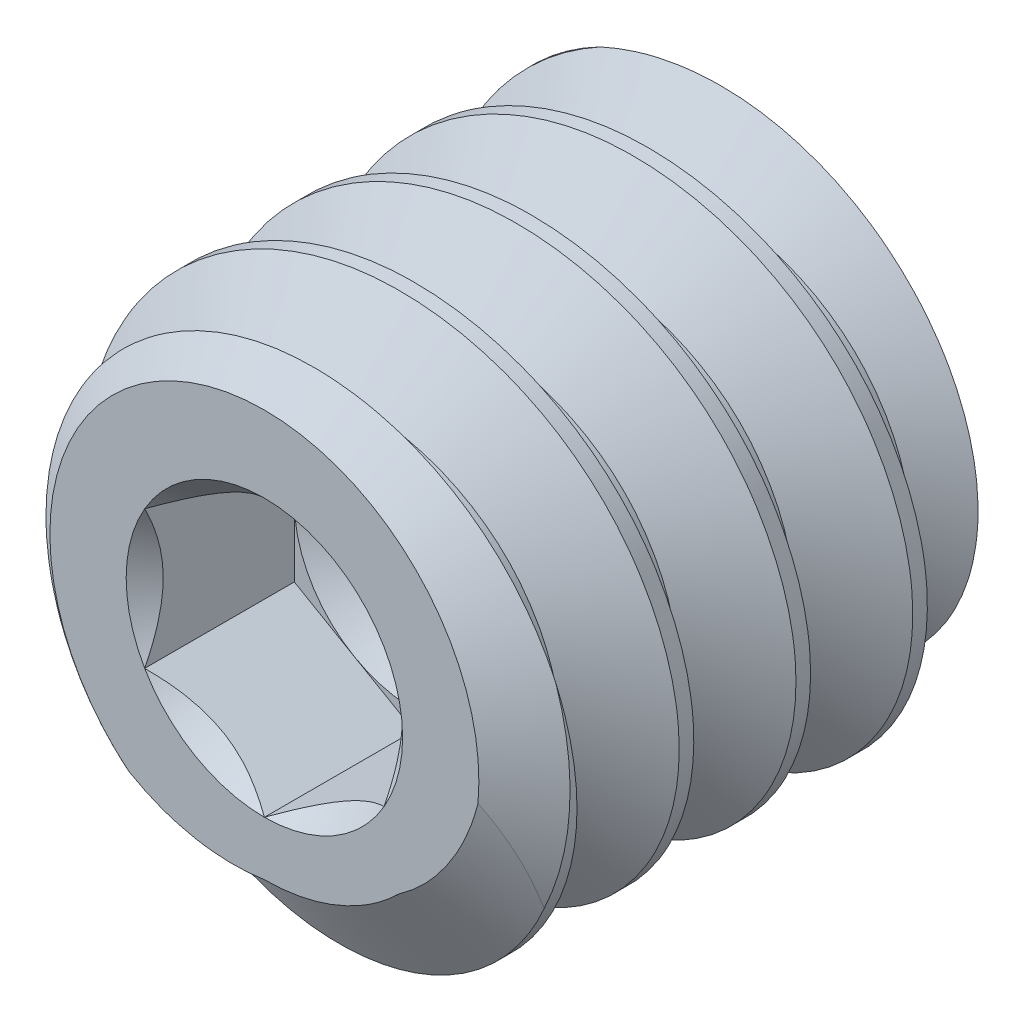
SolidWorks part; units mm, degrees
ref_plane "Front" through (0, 0, 0) normal (0, 0, 1) x (1, 0, 0)
ref_plane "Top" through (0, 0, 0) normal (0, 1, 0) x (1, 0, 0)
ref_plane "Right" through (0, 0, 0) normal (1, 0, 0) x (0, 0, -1)
sketch "Sketch22" plane through (0, 0, 0) normal (1, 0, 0) x (0, 0, -1)
  line L0 (-1.5875, 0) -> (-1.5875, 1.1379)
  line L1 (-1.5875, 1.1379) -> (-1.3883, 1.4224)
  line L2 (-1.3883, 1.4224) -> (0.8439, 1.4224)
  line L3 (0.8439, 1.4224) -> (1.5875, 0.1849)
  line L4 (-1.5875, 1.1379) -> (-1.5875, -1.1379) construction
  line L5 (1.5875, 0) -> (-1.5875, 0)
  line L6 (0, 1.4224) -> (0, -1.4224) construction
  line L8 (1.5875, 0.1849) -> (1.5875, 0)
  line L9 (-1.5875, -1.4224) -> (1.5875, -1.4224) construction
  line L10 (1.5875, 0.1849) -> (1.5875, -0.1849) construction
  line L11 (1.5875, -0.1849) -> (0.8439, -1.4224) construction
  line L13 (1.5875, 0.1849) -> (1.4764, 0) construction
  line L15 (1.4764, 0) -> (1.5875, -0.1849) construction
  dimension "D1" = 118
  dimension "Dia" = 2.8448
  dimension "D2" = 0.3698
  dimension "Length" = 3.175
  dimension "D3" = 35
  dimension "D4" = 118
  dimension "D7" = 2.2758
revolve "Revolve1" add sketch "Sketch22" angle 360 about L5
ref_plane "Plane1" through (0, 0, -1.5875) normal (0, 0, 1) x (1, 0, 0)
sketch "Sketch27" plane through (0, 0, -1.5875) normal (0, 0, 1) x (1, 0, 0)
  circle A0 centre (0, 0) radius 1.4224 construction
  circle A1 centre (0, 0) radius 1.4224
curve "Helix/Spiral1" pitch 0.6195 height 3.7945 radius 1.4224 centre (0, 0, -1.5875) axis (0, 0, 1) start towards (0, 1, 0)
sketch "Sketch28" plane through (0, 0, 0) normal (1, 0, 0) x (0, 0, -1)
  line L0 (1.5875, 1.4224) -> (2.1296, 1.4224)
  line L1 (2.1296, 1.4224) -> (1.8973, 1.02)
  line L2 (1.8973, 1.02) -> (1.8198, 1.02)
  line L3 (1.8198, 1.02) -> (1.5875, 1.4224)
  line L4 (1.7037, 1.2212) -> (2.0134, 1.2212) construction
  line L6 (-1.3883, 1.4224) -> (0.8439, 1.4224) construction
  line L7 (1.5875, 1.6056) -> (1.5875, -1.6056) construction
  dimension "D1" = 0.0774
  dimension "D2" = 0.3098
  dimension "D3" = 60
sweep "Cut-Sweep2" cut profiles "Sketch28" path "Helix/Spiral1" align with end faces yes
sketch "Sketch23" plane through (0, 0, 1.5875) normal (0, 0, 1) x (1, 0, 0)
  line L1 (0, 0.7332) -> (-0.635, 0.3666)
  line L2 (-0.635, 0.3666) -> (-0.635, -0.3666)
  line L3 (-0.635, -0.3666) -> (0, -0.7332)
  line L4 (0, -0.7332) -> (0.635, -0.3666)
  line L5 (0.635, -0.3666) -> (0.635, 0.3666)
  line L6 (0.635, 0.3666) -> (0, 0.7332)
  circle A0 centre (0, 0) radius 0.635 construction
  dimension "Hex" = 1.27
extrude "Cut-Extrude10" cut sketch "Sketch23" against normal blind 0.7937
sketch "Sketch24" plane through (0, 0, 1.5875) normal (0, 0, 1) x (1, 0, 0)
  circle A0 centre (0, 0) radius 0.7332
extrude "Cut-Extrude11" cut sketch "Sketch24" against normal through all draft 45
sketch "Sketch26" plane through (0, 0, 0.7937) normal (0, 0, 1) x (1, 0, 0)
  circle A0 centre (0, 0) radius 0.635 construction
  circle A1 centre (0, 0) radius 0.635
extrude "Cut-Extrude12" cut sketch "Sketch26" against normal through all draft 60
sketch "Sketch30" plane through (0, 0, 0) normal (1, 0, 0) x (0, 0, -1)
  line L0 (-1.3883, 1.4224) -> (0.8439, 1.4224) construction
  line L1 (-1.5875, 0) -> (-1.5875, 1.1379) construction
  line L3 (-1.5875, -1.4224) -> (1.5875, -1.4224) construction
  point P0 (-1.5875, 1.4224)
  point P1 (0.8439, 1.4224)
  point P2 (0.8439, -1.4224)
  point P11 (-0.0853, -1.4224)
  dimension "D1" = 0.9293
equation "\"D7@Sketch22\"=\"Dia@Sketch22\"*.8"
equation "\"D1@Sketch28\" = \"D4@Helix/Spiral1\" * .125"
equation "\"D3@Helix/Spiral1\" = \"Length@Sketch22\" + \"D4@Helix/Spiral1\""
equation "\"D1@Sketch30\" = \"D4@Helix/Spiral1\" * 1.5"
equation "\"hex Depth@Cut-Extrude10\" = \"Hex@Sketch23\" * .625"
equation "\"D2@Sketch28\" = \"D4@Helix/Spiral1\" * .5"
equation "\"D2@Sketch22\" = \"Dia@Sketch22\" * .13"
equation "\"D4@Sketch22\" = \"D1@Sketch22\""
